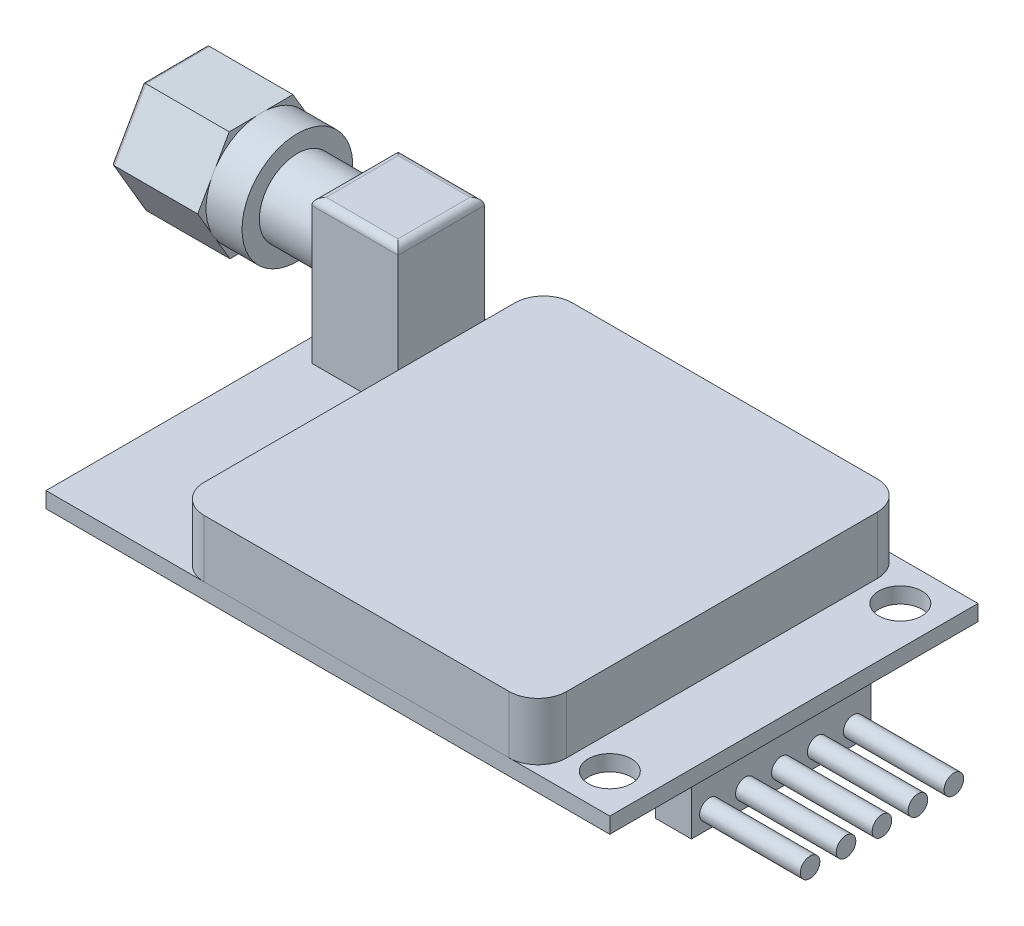
SolidWorks part; units mm, degrees
ref_plane "前视基准面" through (0, 0, 0) normal (0, 0, 1) x (1, 0, 0)
ref_plane "上视基准面" through (0, 0, 0) normal (0, 1, 0) x (1, 0, 0)
ref_plane "右视基准面" through (0, 0, 0) normal (1, 0, 0) x (0, 0, -1)
sketch "草图1" plane through (0, 0, 0) normal (0, 1, 0) x (1, 0, 0)
  line L0 (-24.9996, 0) -> (29.7017, 0) construction
  line L1 (-19.6, 12.8) -> (19.6, 12.8)
  line L2 (-19.6, 12.8) -> (-19.6, -12.8)
  line L3 (-19.6, -12.8) -> (19.6, -12.8)
  line L4 (19.6, 12.8) -> (19.6, -12.8)
  line L7 (-10.6, 12.8) -> (14.6, 12.8)
  line L8 (-10.6, 12.8) -> (-10.6, -12.8)
  line L9 (-10.6, -12.8) -> (14.6, -12.8)
  line L10 (14.6, 12.8) -> (14.6, -12.8)
  circle A0 centre (16.9, 10.1) radius 1.5
  circle A1 centre (16.9, -10.1) radius 1.5
  point P0 (0, 0)
  point P6 (2, 0)
  dimension "D5" = 2.7
  dimension "D6" = 2.7
  dimension "D1" = 25.6
  dimension "D2" = 39.2
  dimension "D3" = 5
  dimension "D4" = 9
extrude "凸台-拉伸1" add sketch "草图1" against normal blind 1.1 contours A0 | L2 L3 L4 L1 | A1 region at (16.9, 0, -10.1)
extrude "凸台-拉伸3" add sketch "草图1<4>" along normal blind 4 separate body contours L8 L9 L10 L7
sketch "草图1<4>" plane through (0, 0, 0) normal (0, 1, 0) x (1, 0, 0) same geometry as "草图1"
fillet "圆角1" radius 2 4 edges at (-10.6, 2, -12.8) (14.6, 2, -12.8) (14.6, 2, 12.8) (-10.6, 2, 12.8)
sketch "草图2" plane through (0, 0, 0) normal (0, 1, 0) x (1, 0, 0)
  line L0 (-19.6, 12.8) -> (19.6, 12.8) construction
  line L1 (-18.02, 10.1) -> (-12.02, 10.1)
  line L2 (-18.02, 10.1) -> (-18.02, 4.1)
  line L3 (-18.02, 4.1) -> (-12.02, 4.1)
  line L4 (-12.02, 10.1) -> (-12.02, 4.1)
  line L5 (-18.02, 10.1) -> (-12.02, 4.1) construction
  line L6 (-18.02, 4.1) -> (-12.02, 10.1) construction
  line L7 (-19.6, 12.8) -> (-19.6, -12.8) construction
  point P0 (-15.02, 7.1)
  dimension "D1" = 6
  dimension "D2" = 6
  dimension "D3" = 2.7
  dimension "D4" = 1.58
extrude "凸台-拉伸4" add sketch "草图2" along normal blind 10 separate body
fillet "圆角2" radius 0.5 4 edges at (-12.02, 10, -7.1) (-15.02, 10, -10.1) (-18.02, 10, -7.1) (-15.02, 10, -4.1)
sketch "草图3" plane through (-18.02, 0, 0) normal (-1, 0, 0) x (0, 0, 1)
  line L0 (-4.1, 9.5) -> (-4.1, 0) construction
  line L1 (-10.1, 9.5) -> (-4.1, 9.5) construction
  line L2 (-10.1, 9.5) -> (-10.1, 3.4761) construction
  line L3 (-10.1, 3.4761) -> (-4.1, 3.4761) construction
  line L4 (-4.1, 9.5) -> (-4.1, 3.4761) construction
  circle A0 centre (-7.1, 6.4881) radius 2.65
  dimension "D1" = 5.3
extrude "凸台-拉伸5" add sketch "草图3" along normal blind 4
sketch "草图4" plane through (-22.02, 0, 0) normal (-1, 0, 0) x (0, 0, 1)
  circle A0 centre (-7.1, 6.4881) radius 3.85
extrude "凸台-拉伸6" add sketch "草图4" along normal blind 2.5
sketch "草图5" plane through (-24.52, 0, 0) normal (-1, 0, 0) x (0, 0, 1)
  line L1 (-4.9105, 2.6381) -> (-2.6711, 6.4592)
  line L2 (-2.6711, 6.4592) -> (-4.8605, 10.3092)
  line L3 (-4.8605, 10.3092) -> (-9.2895, 10.3381)
  line L4 (-9.2895, 10.3381) -> (-11.5289, 6.5169)
  line L5 (-11.5289, 6.5169) -> (-9.3395, 2.6669)
  line L6 (-9.3395, 2.6669) -> (-4.9105, 2.6381)
  circle A0 centre (-7.1, 6.4881) radius 4.429 construction
extrude "凸台-拉伸7" add sketch "草图5" along normal blind 6
sketch "草图6" plane through (-30.52, 0, 0) normal (-1, 0, 0) x (0, 0, 1)
  circle A0 centre (-7.075, 6.4734) radius 3.15
  dimension "D1" = 6.3
extrude "切除-拉伸1" cut sketch "草图6" against normal blind 5
fillet "圆角3" radius 0.2 6 edges at (-30.52, 8.3842, -3.7658) (-30.52, 4.5486, -3.7908) (-30.52, 2.6525, -7.125) (-30.52, 4.5919, -10.4342) (-30.52, 8.4275, -10.4092) (-30.52, 10.3236, -7.075)
sketch "草图7" plane through (0, -1.1, 0) normal (0, -1, 0) x (-1, 0, 0)
  line L0 (25.1711, 0) -> (-28.3765, 0) construction
  line L2 (-16.2236, -6.25) -> (-18.7236, -6.25)
  line L3 (-16.2236, -6.25) -> (-16.2236, 6.25)
  line L4 (-16.2236, 6.25) -> (-18.7236, 6.25)
  line L5 (-18.7236, -6.25) -> (-18.7236, 6.25)
  line L6 (-16.2236, -6.25) -> (-18.7236, 6.25) construction
  line L7 (-16.2236, 6.25) -> (-18.7236, -6.25) construction
  point P3 (-17.4736, 0)
  dimension "D1" = 2.5
  dimension "D2" = 12.5
extrude "凸台-拉伸8" add sketch "草图7" along normal blind 4 separate body
sketch "草图8" plane through (18.7236, 0, 0) normal (1, 0, 0) x (0, 0, -1)
  line L0 (-6.25, -5.1) -> (-6.25, -1.1) construction
  circle A0 centre (-5, -3.9238) radius 0.68
  circle A1 centre (-2.5, -3.9238) radius 0.68
  circle A2 centre (0, -3.9238) radius 0.68
  circle A3 centre (2.5, -3.9238) radius 0.68
  circle A4 centre (5, -3.9238) radius 0.68
  dimension "D1" = 1.25
  dimension "D2" = 5
extrude "凸台-拉伸9" add sketch "草图8" along normal blind 7
sketch "草图9" plane through (0, -1.1, 0) normal (0, -1, 0) x (1, 0, 0)
  line L1 (2.8454, 5.8764) -> (12.6093, 5.8764)
  line L2 (2.8454, 5.8764) -> (2.8454, -7.7448)
  line L3 (2.8454, -7.7448) -> (12.6093, -7.7448)
  line L4 (12.6093, 5.8764) -> (12.6093, -7.7448)
  line L5 (2.8454, 5.8764) -> (12.6093, -7.7448) construction
  line L6 (2.8454, -7.7448) -> (12.6093, 5.8764) construction
  point P0 (7.7273, -0.9342)
extrude "凸台-拉伸10" add sketch "草图9" along normal blind 2
